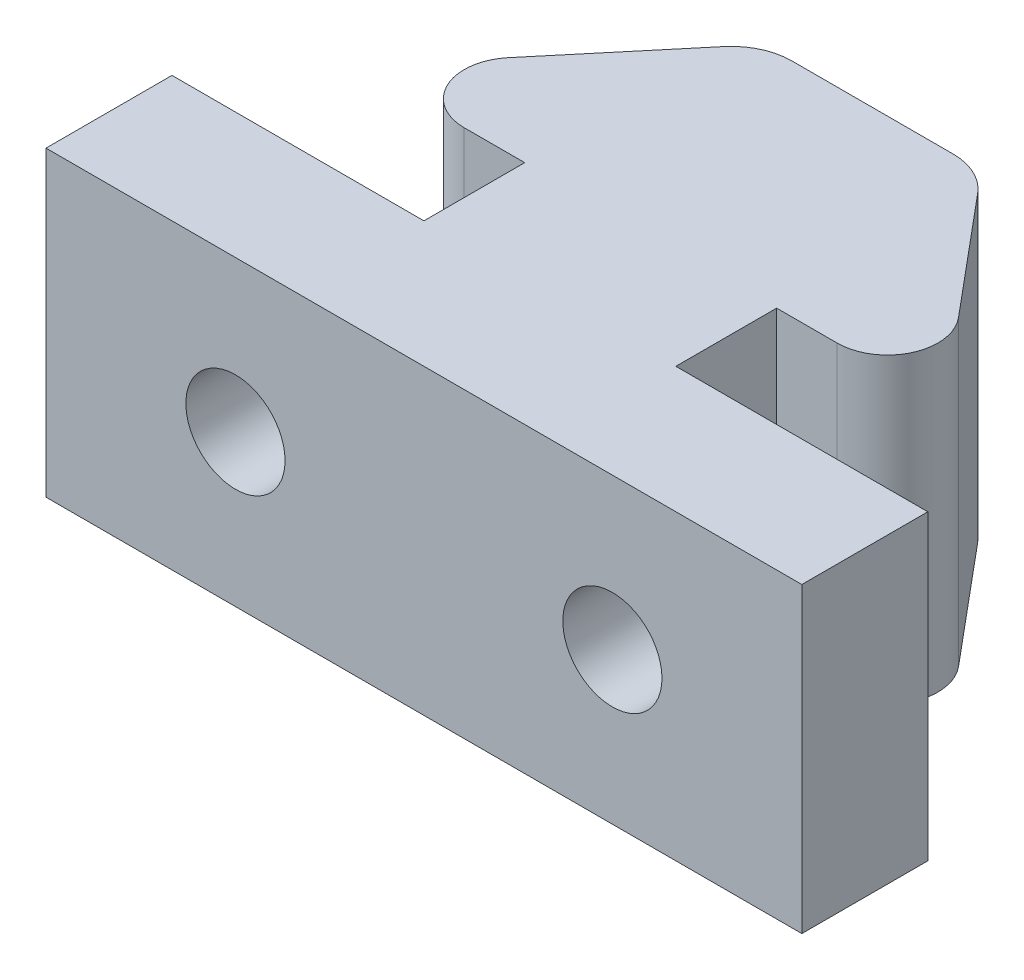
SolidWorks part; units mm, degrees
ref_plane "Front Plane" through (0, 0, 0) normal (0, 0, 1) x (1, 0, 0)
ref_plane "Top Plane" through (0, 0, 0) normal (0, 1, 0) x (1, 0, 0)
ref_plane "Right Plane" through (0, 0, 0) normal (1, 0, 0) x (0, 0, -1)
sketch "Sketch1" plane through (0, 0, 0) normal (0, 0, 1) x (1, 0, 0)
  line L0 (-9.525, 0) -> (9.525, 0) construction
  line L1 (-9.525, -3.81) -> (9.525, -3.81)
  line L2 (-9.525, -3.81) -> (-9.525, 3.81)
  line L3 (-9.525, 3.81) -> (9.525, 3.81)
  line L4 (9.525, -3.81) -> (9.525, 3.81)
  line L5 (-9.525, -3.81) -> (9.525, 3.81) construction
  line L6 (-9.525, 3.81) -> (9.525, -3.81) construction
  line L8 (-9.525, 3.81) -> (0, 3.81)
  point P0 (0, 0)
  dimension "D1" = 7.62
  dimension "D2" = 19.05
extrude "Boss-Extrude1" add sketch "Sketch1" along normal blind 3.175 contours L2 L1 L4 L3
sketch "Sketch2" plane through (0, 3.81, 0) normal (0, 1, 0) x (1, 0, 0)
  line L0 (0, 0) -> (0, 8.128) construction
  line L1 (3.175, 0) -> (3.175, 2.54)
  line L2 (-9.525, 0) -> (9.525, 0) construction
  line L3 (3.175, 2.54) -> (4.6994, 2.54)
  line L4 (5.6737, 4.6247) -> (3.2011, 7.5816)
  line L5 (2.032, 8.128) -> (-2.032, 8.128)
  line L6 (3.175, 0) -> (-3.175, 0)
  line L7 (-3.175, 0) -> (-3.175, 2.54)
  line L8 (-3.175, 2.54) -> (-4.6994, 2.54)
  line L9 (-5.6737, 4.6247) -> (-3.2011, 7.5816)
  arc A0 (3.2011, 7.5816) -> (2.032, 8.128) centre (2.032, 6.604) ccw
  arc A1 (4.6994, 2.54) -> (5.6737, 4.6247) centre (4.6994, 3.81) ccw
  arc A2 (-4.6994, 2.54) -> (-5.6737, 4.6247) centre (-4.6994, 3.81) cw
  arc A3 (-3.2011, 7.5816) -> (-2.032, 8.128) centre (-2.032, 6.604) cw
  point P19 (2.7442, 8.128)
  point P22 (7.4168, 2.54)
  point P25 (-7.4168, 2.54)
  point P28 (-2.7442, 8.128)
  dimension "D5" = 1.524
  dimension "D7" = 1.27
  dimension "D1" = 8.128
  dimension "D2" = 6.35
  dimension "D3" = 5.588
  dimension "D4" = 14.8336
  dimension "D6" = 4.064
extrude "Boss-Extrude2" add sketch "Sketch2" against normal up to surface (7.62 mm away) up to face at (0, -3.81, 1.5875)
sketch "Sketch3" plane through (0, 0, 3.175) normal (0, 0, 1) x (1, 0, 0)
  line L0 (0, 3.81) -> (0, -3.81) construction
  line L1 (-9.525, 3.81) -> (9.525, 3.81) construction
  line L2 (-9.525, -3.81) -> (9.525, -3.81) construction
  circle A0 centre (-4.75, 0) radius 1.25
  circle A1 centre (4.75, 0) radius 1.25
  dimension "D2" = 2.5
  dimension "D1" = 9.5
extrude "Cut-Extrude1" cut sketch "Sketch3" against normal up to surface (3.175 mm away) up to face at (6.35, 0, 0)
